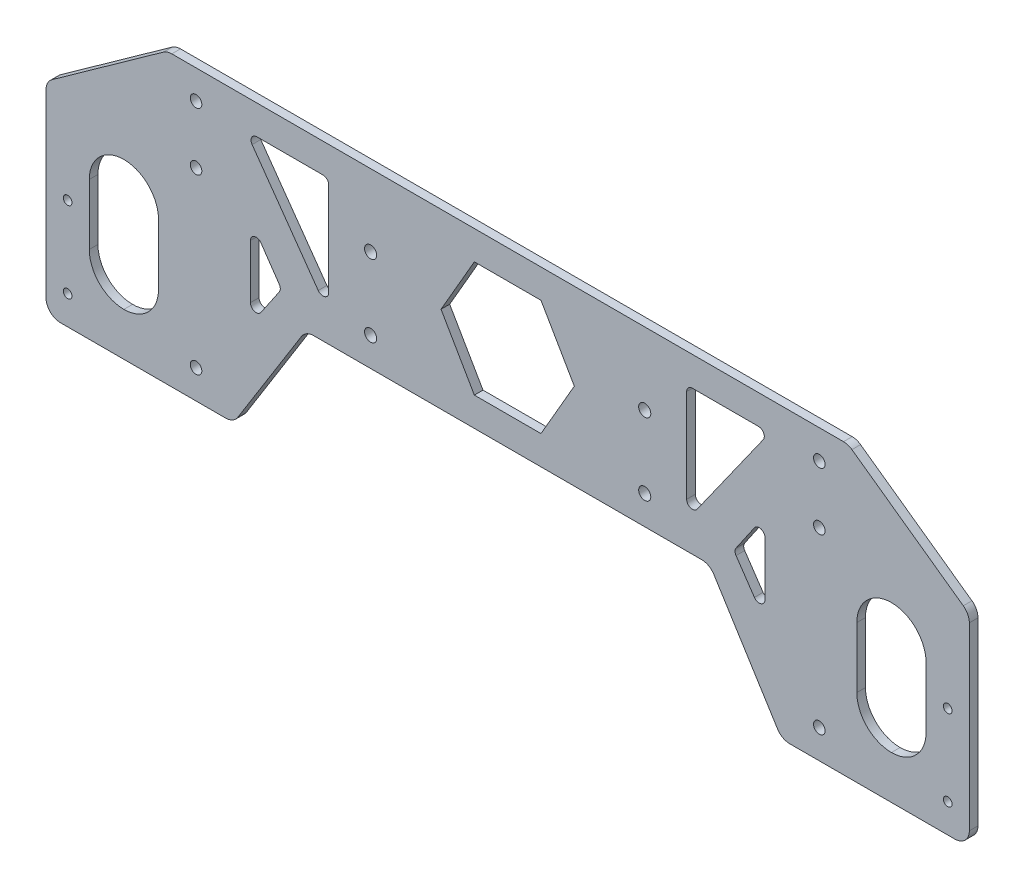
SolidWorks part; units mm, degrees
ref_plane "前视基准面" through (0, 0, 0) normal (0, 0, 1) x (1, 0, 0)
ref_plane "上视基准面" through (0, 0, 0) normal (0, 1, 0) x (1, 0, 0)
ref_plane "右视基准面" through (0, 0, 0) normal (1, 0, 0) x (0, 0, -1)
sketch "草图1" plane through (0, 0, 0) normal (0, 0, 1) x (1, 0, 0)
  line L1 (-160, 50) -> (160, 50)
  line L2 (-160, 50) -> (-160, -50)
  line L3 (-160, -50) -> (160, -50)
  line L4 (160, 50) -> (160, -50)
  line L5 (-160, 50) -> (160, -50) construction
  line L6 (-160, -50) -> (160, 50) construction
  point P0 (0, 0)
extrude "凸台-拉伸1" add sketch "草图1" along normal blind 3
ref_plane "基准面1" through (0, 0, 0) normal (1, 0, 0) x (0, 0, -1)
hole_wizard "Ø4.0 (4) 直径孔1" positions "草图3" profile "草图2" hole size "Ø4.0" standard "GB" end condition through all
sketch "草图3" plane through (0, 0, 0) normal (0, 0, -1) x (-1, 0, 0)
  line L0 (0, -50) -> (0, -40)
  line L1 (160, -50) -> (-160, -50) construction
  line L2 (0, -40) -> (108, -40)
  point P0 (108, -40)
sketch "草图2" plane through (-108, -40, 0) normal (1, 0, 0) x (0, 1, 0)
  line L0 (0, 0) -> (0, 3)
  line L1 (0, 3) -> (2, 3)
  line L2 (2, 3) -> (2, 0)
  line L5 (2, 0) -> (0, 0)
  line L11 (0, -6.35) -> (0, 107.95) construction
  dimension "通孔孔直径" = 4
  dimension "通孔孔深度" = 3
mirror "镜向1" about plane through (0, 0, 0) normal (1, 0, 0) of "Ø4.0 (4) 直径孔1"
hole_wizard "Ø4.2 (4.2) 直径孔1" positions "草图5" profile "草图4" hole size "Ø4.2" standard "GB" end condition through all
sketch "草图5" plane through (0, 0, 0) normal (0, 0, -1) x (-1, 0, 0)
  line L1 (0, -50) -> (47.5, -50)
  line L2 (160, -50) -> (-160, -50) construction
  line L3 (47.5, -50) -> (47.5, 0)
  point P7 (47.5, 0)
sketch "草图4" plane through (-47.5, 0, 0) normal (1, 0, 0) x (0, 1, 0)
  line L0 (0, 0) -> (0, 3)
  line L1 (0, 3) -> (2.1, 3)
  line L2 (2.1, 3) -> (2.1, 0)
  line L5 (2.1, 0) -> (0, 0)
  line L11 (0, -6.35) -> (0, 107.95) construction
  dimension "通孔孔直径" = 4.2
  dimension "通孔孔深度" = 3
pattern_linear "阵列(线性)1" count 2 spacing 95 along (1, 0, 0) count 2 spacing 25 along (0, 1, 0) of "Ø4.2 (4.2) 直径孔1"
sketch "草图6" plane through (0, 0, 0) normal (0, 0, -1) x (-1, 0, 0)
  line L0 (0, -50) -> (0, -10)
  line L1 (160, -50) -> (-160, -50) construction
  line L2 (0, -10) -> (70, -10)
  line L3 (70, -10) -> (95, -50)
  line L4 (95, -50) -> (0, -50)
extrude "切除-拉伸1" cut sketch "草图6" against normal blind 3
mirror "镜向2" about plane through (0, -50, 3) normal (1, 0, 0) of "切除-拉伸1"
sketch "草图8" plane through (0, 0, 0) normal (0, 0, -1) x (-1, 0, 0)
  line L0 (-160, -50) -> (-145, -50)
  line L1 (-95, -50) -> (-160, -50) construction
  line L2 (-145, -50) -> (-145, -35)
  line L3 (-145, -35) -> (-121, -35)
  line L4 (-121, -35) -> (-121, 10)
  line L5 (-121, 10) -> (-145, 10)
  line L6 (-145, 10) -> (-145, -35)
extrude "切除-拉伸6" cut sketch "草图8" against normal blind 3 contours L5 L6 L3 L4 region at (133, -12.5, 0)
mirror "镜向4" about plane through (0, 0, 0) normal (1, 0, 0) of "切除-拉伸6"
pattern_linear "阵列(线性)2" count 2 spacing 60 along (0, 1, 0) of "镜向1"
hole_wizard "Ø3.0 (3) 直径孔1" positions "草图10" profile "草图9" hole size "Ø3.0" standard "GB" end condition through all
sketch "草图10" plane through (0, 0, 3) normal (0, 0, 1) x (1, 0, 0)
  line L5 (-152.5, -40) -> (-152.5, -12)
  line L7 (-152.5, -50) -> (-152.5, -40)
  line L8 (-160, -50) -> (-95, -50) construction
  point P0 (-152.5, -40)
  point P2 (-152.5, -12)
sketch "草图9" plane through (-152.5, -40, 3) normal (1, 0, 0) x (0, -1, 0)
  line L0 (0, 0) -> (0, 3)
  line L1 (0, 3) -> (1.5, 3)
  line L2 (1.5, 3) -> (1.5, 0)
  line L5 (1.5, 0) -> (0, 0)
  line L11 (0, -6.35) -> (0, 107.95) construction
  dimension "通孔孔直径" = 3
  dimension "通孔孔深度" = 3
sketch "草图11" plane through (0, 0, 3) normal (0, 0, 1) x (1, 0, 0)
  line L0 (-160, 50) -> (-160, 20)
  line L1 (-160, 50) -> (-160, -50) construction
  line L2 (-160, 20) -> (-118, 50)
  line L3 (160, 50) -> (-160, 50) construction
  line L4 (-118, 50) -> (-160, 50)
  line L5 (-160, -50) -> (-160, 20)
  line M22 (160, 50) -> (-160, 50)
  line M23 (-160, 50) -> (-160, -50)
extrude "切除-拉伸8" cut sketch "草图11" against normal blind 3 contours L2 M23 M22 region at (-146, 40, 3)
mirror "镜向6" about plane through (0, 0, 0) normal (1, 0, 0) of "切除-拉伸8"
mirror "镜向7" about plane through (0, 0, 0) normal (1, 0, 0) of "Ø3.0 (3) 直径孔1"
fillet "圆角1" radius 12 8 edges at (145, -35, 1.5) (121, -35, 1.5) (145, 10, 1.5) (121, 10, 1.5) (-145, -35, 1.5) (-121, -35, 1.5) (-145, 10, 1.5) (-121, 10, 1.5)
pattern_linear "阵列(线性)3" count 2 spacing 80 along (0, 1, 0) of "镜向1"
fillet "圆角2" radius 5 10 edges at (118, 50, 1.5) (160, 20, 1.5) (-118, 50, 1.5) (-160, 20, 1.5) (-160, -50, 1.5) (-95, -50, 1.5) (-70, -10, 1.5) (160, -50, 1.5) (70, -10, 1.5) (95, -50, 1.5)
sketch "草图12" plane through (0, 0, 0) normal (0, 0, -1) x (-1, 0, 0)
  line L0 (-89.1673, -17.5674) -> (-78.3816, -1.6764)
  line L1 (-89.1673, -17.5674) -> (-89.1673, 14.0344)
  line L2 (-89.1673, 14.0344) -> (-78.3816, -1.6764)
  line L3 (-90.8041, 39.841) -> (-62.0227, 39.841)
  line L4 (-62.0227, 39.841) -> (-62.0227, -0.7784)
  line L5 (-62.0227, -0.7784) -> (-90.8041, 39.841)
extrude "切除-拉伸9" cut sketch "草图12" against normal blind 3
mirror "镜向8" about plane through (0, 0, 0) normal (1, 0, 0) of "切除-拉伸9"
fillet "圆角3" radius 2 12 edges at (-90.8041, 39.841, 1.5) (-62.0227, 39.841, 1.5) (-89.1673, 14.0344, 1.5) (-78.3816, -1.6764, 1.5) (-62.0227, -0.7784, 1.5) (-89.1673, -17.5674, 1.5) (90.8041, 39.841, 1.5) (62.0227, 39.841, 1.5) (62.0227, -0.7784, 1.5) (89.1673, 14.0344, 1.5) (78.3816, -1.6764, 1.5) (89.1673, -17.5674, 1.5)
sketch "草图13" plane through (0, 0, 3) normal (0, 0, 1) x (1, 0, 0)
  line L0 (0, -10) -> (0, 20) construction
  line L1 (-67.2288, -10) -> (67.2288, -10) construction
  line L3 (-23.094, 20) -> (-11.547, 0)
  line L4 (-11.547, 0) -> (11.547, 0)
  line L5 (11.547, 0) -> (23.094, 20)
  line L6 (23.094, 20) -> (11.547, 40)
  line L7 (11.547, 40) -> (-11.547, 40)
  line L8 (-11.547, 40) -> (-23.094, 20)
  circle A0 centre (0, 20) radius 20 construction
extrude "切除-拉伸10" cut sketch "草图13" against normal blind 10
